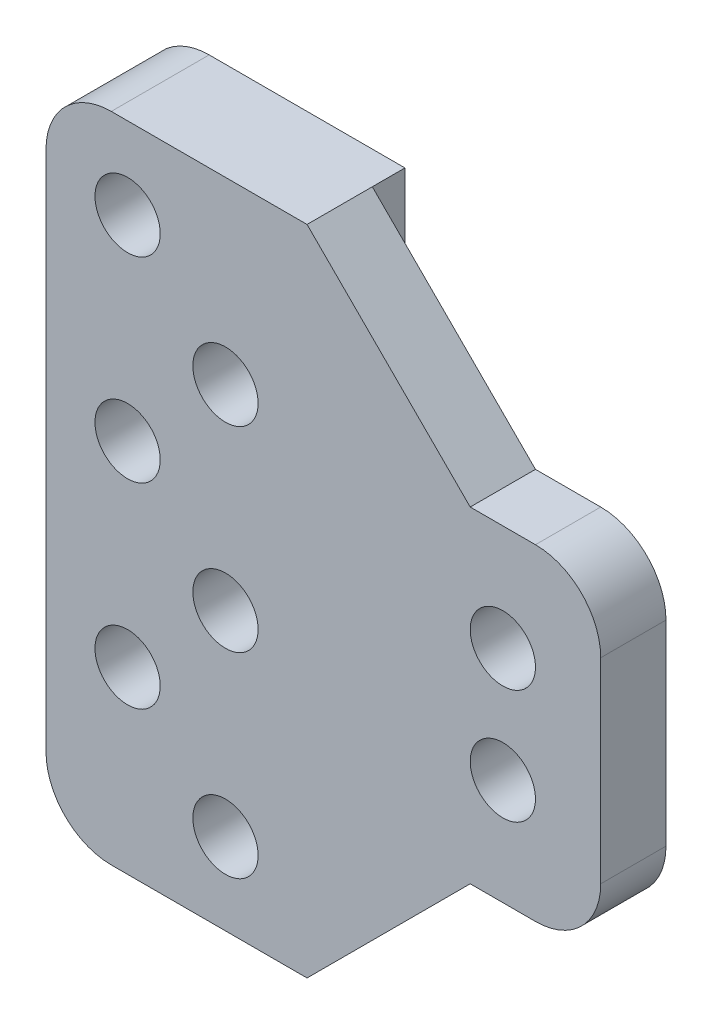
SolidWorks part; units mm, degrees
material "Delrin 2700 NC010, Low Viscosity Acetal Copolymer (SS)"
ref_plane "Front Plane" through (0, 0, 0) normal (0, 0, 1) x (1, 0, 0)
ref_plane "Top Plane" through (0, 0, 0) normal (0, 1, 0) x (1, 0, 0)
ref_plane "Right Plane" through (0, 0, 0) normal (1, 0, 0) x (0, 0, -1)
sketch "Sketch1" plane through (0, 0, 0) normal (0, 0, 1) x (1, 0, 0)
  line L0 (0, 5) -> (0, -5) construction
  line L1 (-3, 5) -> (3, 5)
  line L2 (-3, 5) -> (-3, -5)
  line L3 (-3, -5) -> (3, -5)
  line L4 (3, 5) -> (3, -5)
  line L5 (-3, 5) -> (3, -5) construction
  line L6 (-3, -5) -> (3, 5) construction
  circle A0 centre (0, 1.75) radius 1
  circle A1 centre (0, -1.75) radius 1
  dimension "D3" = 2
  dimension "D4" = 2
  dimension "D1" = 6
  dimension "D2" = 10
  dimension "D5" = 3.5
  dimension "D6" = 1.75
extrude "Boss-Extrude1" add sketch "Sketch1" along normal blind 2
sketch "Sketch2" plane through (0, 0, 2) normal (0, 0, 1) x (1, 0, 0)
  line L1 (-14, -10) -> (-14, 10)
  line L2 (-14, 10) -> (-6, 10)
  line L3 (-6, 10) -> (-6, 5)
  line L4 (-6, 5) -> (-3, 5)
  line L5 (-3, 5) -> (-3, -5)
  line L6 (-3, -5) -> (-6, -5)
  line L7 (-6, -5) -> (-6, -10)
  line L8 (-6, -10) -> (-14, -10)
  line L9 (-3, 0) -> (-14, 0) construction
  dimension "D1" = 3
  dimension "D2" = 11
  dimension "D3" = 20
extrude "Boss-Extrude2" add sketch "Sketch2" against normal blind 2
sketch "Sketch3" plane through (0, 0, 0) normal (0, 0, -1) x (-1, 0, 0)
  line L0 (6, 5) -> (6, 10) construction
  line L1 (6, 10) -> (14, 10)
  line L2 (6, 10) -> (6, -10)
  line L3 (6, -10) -> (14, -10)
  line L4 (14, 10) -> (14, -10)
  line L6 (6, -10) -> (6, -5) construction
  line L7 (14, -10) -> (6, -10) construction
  line L8 (14, 10) -> (14, -10) construction
  line L9 (6, 10) -> (14, 10) construction
extrude "Boss-Extrude3" add sketch "Sketch3" along normal blind 1
sketch "Sketch4" plane through (0, 0, 2) normal (0, 0, 1) x (1, 0, 0)
  line L0 (-8.5, 10) -> (-8.5, -5) construction
  line L1 (-6, 10) -> (-14, 10) construction
  line L2 (-6, -5) -> (3, -5) construction
  line L3 (-8.5, -5) -> (-11.5, -5) construction
  line L4 (-11.5, -5) -> (-11.5, 10) construction
  line L5 (-14, 10) -> (-14, -10) construction
  line L6 (-6, 5) -> (-6, 10) construction
  line L7 (-8.5, -7.5) -> (-11.5, -4.5) construction
  line L8 (-14, -10) -> (-6, -10) construction
  circle A0 centre (-8.5, -7.5) radius 1
  circle A1 centre (-11.5, -4.5) radius 1
  dimension "D3" = 2
  dimension "D1" = 2.5
  dimension "D2" = 2.5
  dimension "D4" = 2.5
  dimension "D5" = 3
extrude "Cut-Extrude1" cut sketch "Sketch4" against normal blind 5
pattern_linear "LPattern1" count 3 spacing 6 along (0, 1, 0) of "Cut-Extrude1"
chamfer "Chamfer1" distance 5 angle 45 2 edges at (-6, 5, 1) (-6, -5, 1)
fillet "Fillet1" radius 2 4 edges at (3, 5, 1) (3, -5, 1) (-14, 10, 0.5) (-14, -10, 0.5)
equation "\"D6@Sketch1\"=\"D5@Sketch1\"/2"
